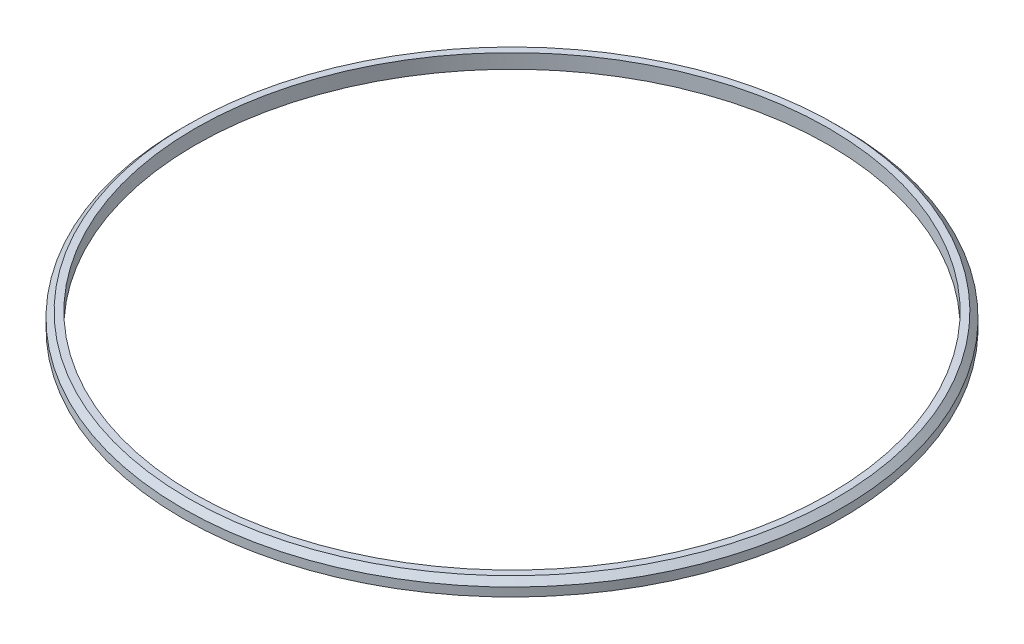
SolidWorks part; units mm, degrees
material "PETG"
ref_plane "Front Plane" through (0, 0, 0) normal (0, 0, 1) x (1, 0, 0)
ref_plane "Top Plane" through (0, 0, 0) normal (0, 1, 0) x (1, 0, 0)
ref_plane "Right Plane" through (0, 0, 0) normal (1, 0, 0) x (0, 0, -1)
sketch "Sketch1" plane through (0, 0, 0) normal (0, 1, 0) x (1, 0, 0)
  circle A0 centre (0, 0) radius 57.2
  circle A1 centre (0, 0) radius 55
  dimension "Ring OD" = 114.4
  dimension "Ring Width" = 2.2
extrude "Boss-Extrude1" add sketch "Sketch1" along normal blind 2.5
chamfer "Chamfer1" distance 1 angle 45 1 edges at (0, 2.5, 57.2)
equation "\"tol_dia_id_intfc\" = 0.100mm ' For hole diameters - Interference fit"
equation "\"tol_dia_id_slip\"  = 0.150mm ' For hole diameters - Slip fit"
equation "\"tol_dia_id_clear\" = 0.200mm ' For hole diameters - Clearance fit"
equation "\"tol_dia_od_intfc\" = 0.100mm ' For shaft diameters - Interference fit"
equation "\"tol_dia_od_slip\"  = 0.150mm ' For shaft diameters - Slip fit"
equation "\"tol_dia_od_clear\" = 0.200mm ' For shaft diameters - Clearance fit"
equation "\"tol_general_intfc\"= 0.050mm ' For general parts (Horiz) - Interference fit"
equation "\"tol_general_slip\" = 0.075mm ' For general parts (Horiz) - Slip fit"
equation "\"tol_general_clear\"= 0.100mm ' For general parts (Horiz) - Clearance fit"
equation "\"tol_layer_intfc\"  = 0.050mm ' For all parts (Vert) - Interference fit"
equation "\"tol_layer_slip\"   = 0.075mm ' For all parts (Vert) - Slip fit"
equation "\"tol_layer_clear\"  = 0.100mm ' For all parts (Vert) - Clearance fit"
equation "\"tol_corner_rad\"   = 0.250mm ' For corners that fit into other parts"
equation "\"Ring OD@Sketch1\" = 114.50mm - \"tol_dia_od_intfc\""
equation "\"Ring Width@Sketch1\" = 2.50mm - \"tol_dia_id_slip\" - \"tol_dia_od_slip\""
